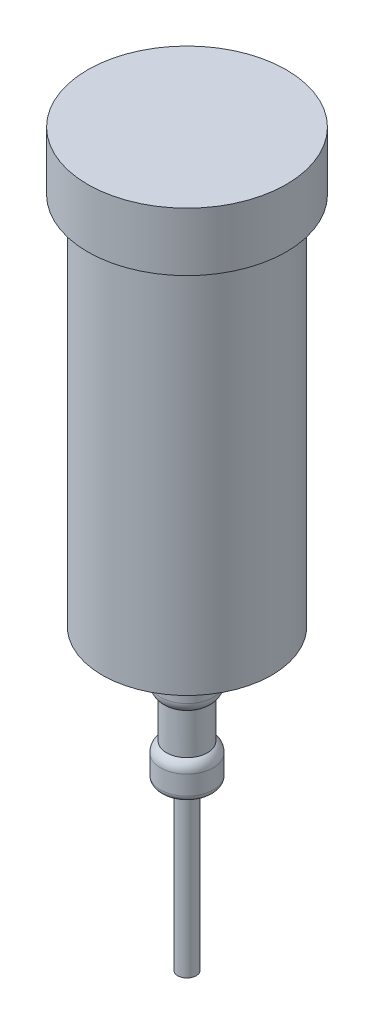
SolidWorks part; units mm, degrees
ref_plane "前视基准面" through (0, 0, 0) normal (0, 0, 1) x (1, 0, 0)
ref_plane "上视基准面" through (0, 0, 0) normal (0, 1, 0) x (1, 0, 0)
ref_plane "右视基准面" through (0, 0, 0) normal (1, 0, 0) x (0, 0, -1)
sketch "草图1" plane through (0, 0, 0) normal (0, 1, 0) x (1, 0, 0)
  circle A0 centre (0, 0) radius 14.5
  dimension "D1" = 29
extrude "凸台-拉伸1" add sketch "草图1" along normal blind 64
sketch "草图2" plane through (0, 0, 0) normal (0, -1, 0) x (1, 0, 0)
  circle A0 centre (0, 0) radius 6
  dimension "D1" = 12
extrude "凸台-拉伸2" add sketch "草图2" along normal blind 4
sketch "草图3" plane through (0, -4, 0) normal (0, -1, 0) x (1, 0, 0)
  circle A0 centre (0, 0) radius 4.5
  dimension "D1" = 9
extrude "凸台-拉伸3" add sketch "草图3" along normal blind 6
sketch "草图5" plane through (0, -10, 0) normal (0, -1, 0) x (1, 0, 0)
  circle A0 centre (0, 0) radius 3.5
  dimension "D1" = 7
extrude "凸台-拉伸4" add sketch "草图5" along normal blind 7
sketch "草图6" plane through (0, -17, 0) normal (0, -1, 0) x (1, 0, 0)
  circle A0 centre (0, 0) radius 4.5
  dimension "D1" = 9
extrude "凸台-拉伸5" add sketch "草图6" along normal blind 6
fillet "圆角1" radius 2 1 edges at (0, -10, -4.5)
fillet "圆角2" radius 2 1 edges at (0, -17, -4.5)
fillet "圆角3" radius 1 1 edges at (0, -23, -4.5)
sketch "草图7" plane through (0, -23, 0) normal (0, -1, 0) x (1, 0, 0)
  circle A0 centre (0, 0) radius 1.5875
  dimension "D1" = 3.175
extrude "切除-拉伸1" cut sketch "草图7" against normal blind 6
sketch "草图8" plane through (0, 64, 0) normal (0, 1, 0) x (1, 0, 0)
  circle A0 centre (0, 0) radius 17
  dimension "D1" = 34
extrude "凸台-拉伸6" add sketch "草图8" along normal blind 10
sketch "草图9" plane through (0, -23, 0) normal (0, -1, 0) x (1, 0, 0)
  circle A0 centre (0, 0) radius 1.5875
  dimension "D1" = 3.175
extrude "凸台-拉伸7" add sketch "草图9" along normal blind 28 separate body
